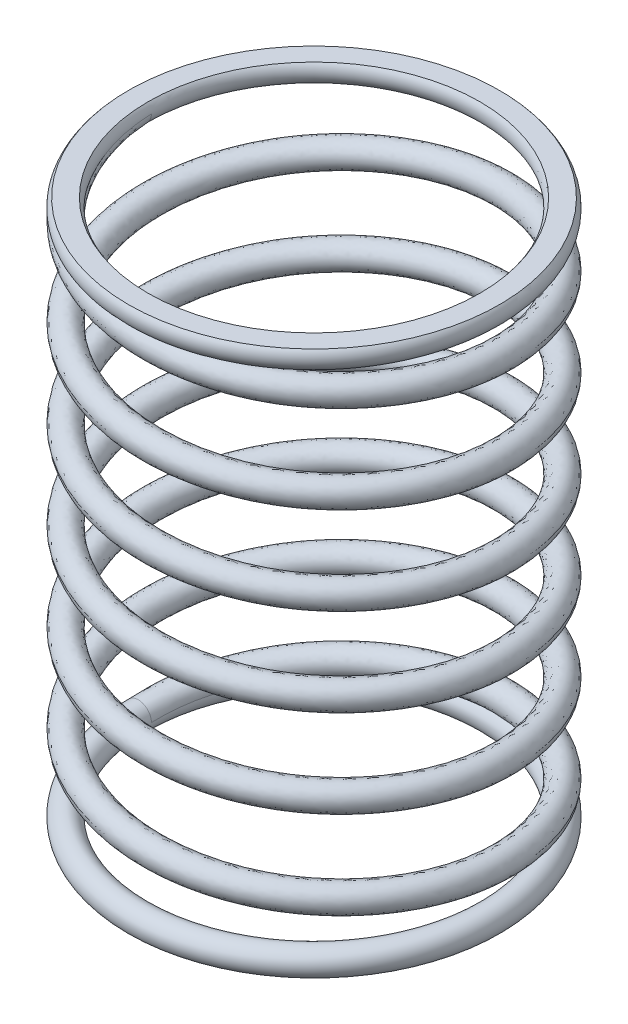
SolidWorks part; units mm, degrees
ref_plane "Plano frontal" through (0, 0, 0) normal (0, 0, 1) x (1, 0, 0)
ref_plane "Plano superior" through (0, 0, 0) normal (0, 1, 0) x (1, 0, 0)
ref_plane "Plano direito" through (0, 0, 0) normal (1, 0, 0) x (0, 0, -1)
sketch "Esboço3" plane through (0, 0, 0) normal (0, 1, 0) x (1, 0, 0)
  circle A0 centre (0, 0) radius 2
  dimension "D1" = 4
curve "Hélice/Espiral1" pitch 1 height 6 radius 2 left hand yes centre (0, 0, 0) axis (0, 1, 0) start towards (0, 0, 1)
sketch "Esboço4" plane through (0, 0, 0) normal (0, 0, 1) x (1, 0, 0)
  circle A0 centre (-2, 0) radius 0.15
  spline S0 degree 3 poles (-2, 0) (-2, 0.0207) (-1.8959, 0.0626) (-1.451, 0.125) (-0.7853, 0.1875) (0, 0.25) (0.7853, 0.3125) (1.451, 0.375) (1.8959, 0.4375) (2.0521, 0.5) (1.8959, 0.5625) (1.451, 0.625) (0.5634, 0.7083) (-0.5634, 0.7917) (-1.451, 0.875) (-1.8959, 0.9375) (-2.0521, 1) (-1.8959, 1.0625) (-1.451, 1.125) (-0.5634, 1.2083) (0.5634, 1.2917) (1.451, 1.375) (1.8959, 1.4375) (2.0521, 1.5) (1.8959, 1.5625) (1.451, 1.625) (0.5634, 1.7083) (-0.5634, 1.7917) (-1.451, 1.875) (-1.8959, 1.9375) (-2.0521, 2) (-1.8959, 2.0625) (-1.451, 2.125) (-0.5634, 2.2083) (0.5634, 2.2917) (1.451, 2.375) (1.8959, 2.4375) (2.0521, 2.5) (1.8959, 2.5625) (1.451, 2.625) (0.5634, 2.7083) (-0.5634, 2.7917) (-1.451, 2.875) (-1.8959, 2.9375) (-2.0521, 3) (-1.8959, 3.0625) (-1.451, 3.125) (-0.5634, 3.2083) (0.5634, 3.2917) (1.451, 3.375) (1.8959, 3.4375) (2.0521, 3.5) (1.8959, 3.5625) (1.451, 3.625) (0.5634, 3.7083) (-0.5634, 3.7917) (-1.451, 3.875) (-1.8959, 3.9375) (-2.0521, 4) (-1.8959, 4.0625) (-1.451, 4.125) (-0.5634, 4.2083) (0.5634, 4.2917) (1.451, 4.375) (1.8959, 4.4375) (2.0521, 4.5) (1.8959, 4.5625) (1.451, 4.625) (0.5634, 4.7083) (-0.5634, 4.7917) (-1.451, 4.875) (-1.8959, 4.9375) (-2.0521, 5) (-1.8959, 5.0625) (-1.451, 5.125) (-0.5634, 5.2083) (0.5634, 5.2917) (1.451, 5.375) (1.8959, 5.4375) (2.0521, 5.5) (1.8959, 5.5625) (1.451, 5.625) (0.7853, 5.6875) (0, 5.75) (-0.7853, 5.8125) (-1.451, 5.875) (-1.8959, 5.9374) (-2, 5.9793) (-2, 6) knots 0 0 0 0 0.010417 0.020833 0.03125 0.041667 0.052083 0.0625 0.072917 0.083333 0.09375 0.104167 0.114583 0.135417 0.145833 0.15625 0.166667 0.177083 0.1875 0.197917 0.21875 0.229167 0.239583 0.25 0.260417 0.270833 0.28125 0.302083 0.3125 0.322917 0.333333 0.34375 0.354167 0.364583 0.385417 0.395833 0.40625 0.416667 0.427083 0.4375 0.447917 0.46875 0.479167 0.489583 0.5 0.510417 0.520833 0.53125 0.552083 0.5625 0.572917 0.583333 0.59375 0.604167 0.614583 0.635417 0.645833 0.65625 0.666667 0.677083 0.6875 0.697917 0.71875 0.729167 0.739583 0.75 0.760417 0.770833 0.78125 0.802083 0.8125 0.822917 0.833333 0.84375 0.854167 0.864583 0.885417 0.895833 0.90625 0.916667 0.927083 0.9375 0.947917 0.958333 0.96875 0.979167 0.989583 1 1 1 1 construction
  dimension "D1" = 2
  dimension "D2" = 0.3
sweep "Varredura1" add profiles "Esboço4" path "Hélice/Espiral1"
sketch "Esboço5" plane through (0, 0, 0) normal (0, 0, 1) x (1, 0, 0)
  circle A0 centre (-2, 0) radius 0.15
sketch "Esboço6" plane through (0, 0, 0) normal (0, 1, 0) x (1, 0, 0)
  circle A0 centre (0, 0) radius 2
  dimension "D1" = 4
sweep "Varredura2" add profiles "Esboço5" path "Esboço6"
ref_plane "Plano1" through (0, 6, 0) normal (0, 1, 0) x (1, 0, 0)
sketch "Esboço7" plane through (0, 6, 0) normal (0, 1, 0) x (1, 0, 0)
  circle A0 centre (0, 0) radius 2
  dimension "D1" = 4
sketch "Esboço8" plane through (0, 0, 0) normal (0, 0, -1) x (-1, 0, 0)
  line L0 (2.365, 6) -> (-2.365, 6) construction
  line L1 (2, 6) -> (-2, 6) construction
  circle A0 centre (2, 6) radius 0.15
sweep "Varredura3" add profiles "Esboço8" path "Esboço7"
sketch "Esboço9" plane through (0, 0, 0) normal (0, 1, 0) x (1, 0, 0)
  circle A0 centre (0, 0) radius 2.15
extrude "Corte-extrusão1" cut sketch "Esboço9" against normal through all from offset 0.1 offset against normal yes
sketch "Esboço10" plane through (0, 6, 0) normal (0, 1, 0) x (1, 0, 0)
  circle A0 centre (0, 0) radius 2.15
extrude "Corte-extrusão2" cut sketch "Esboço10" along normal through all from offset 0.1
